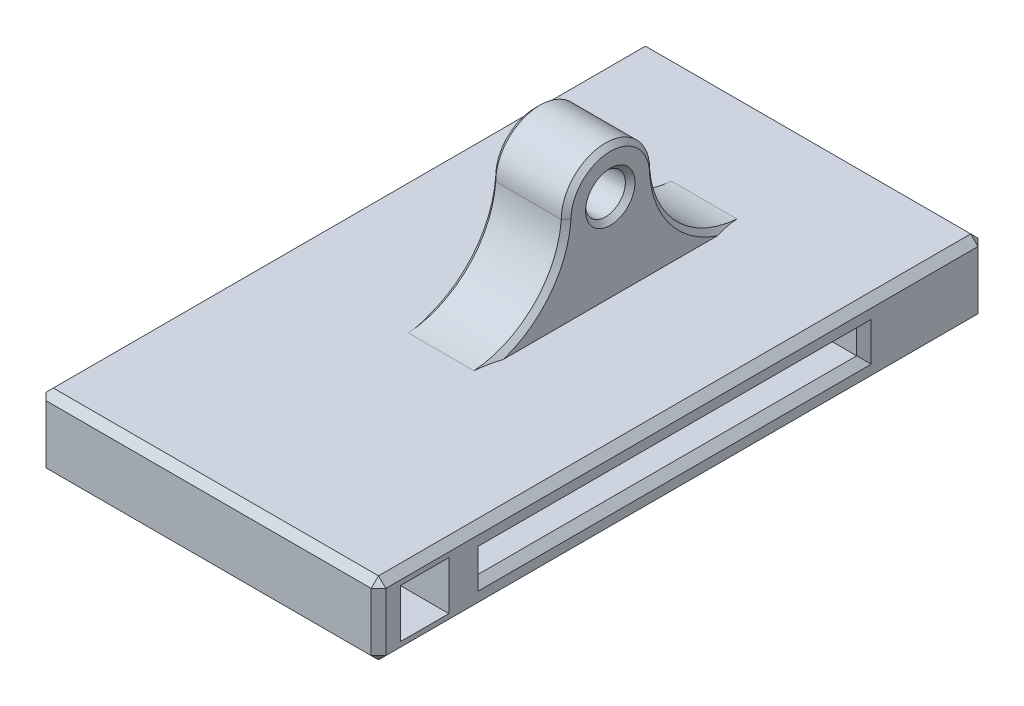
SolidWorks part; units mm, degrees
ref_plane "정면" through (0, 0, 0) normal (0, 0, 1) x (1, 0, 0)
ref_plane "윗면" through (0, 0, 0) normal (0, 1, 0) x (1, 0, 0)
ref_plane "우측면" through (0, 0, 0) normal (1, 0, 0) x (0, 0, -1)
sketch "스케치1" plane through (0, 0, 0) normal (0, 1, 0) x (1, 0, 0)
  line L1 (-35, -30) -> (35, -30)
  line L2 (-35, -30) -> (-35, 30)
  line L3 (-35, 30) -> (35, 30)
  line L4 (35, -30) -> (35, 30)
  line L5 (-35, -30) -> (35, 30) construction
  line L6 (-35, 30) -> (35, -30) construction
  point P0 (0, 0)
  dimension "D1" = 60
  dimension "D2" = 70
extrude "보스-돌출1" add sketch "스케치1" along normal blind 15
sketch "스케치2" plane through (0, 0, 0) normal (1, 0, 0) x (0, 0, -1)
  line L0 (0, 15) -> (0, 33) construction
  line L3 (30, 15) -> (-30, 15)
  circle A0 centre (0, 33) radius 4.1
  circle A1 centre (0, 33) radius 9.1
  arc A2 (9.1, 33) -> (30, 15) centre (28.5463, 34.4457) ccw
  arc A3 (-9.1, 33) -> (-30, 15) centre (-28.5463, 34.4457) cw
  dimension "D1" = 18.2
extrude "보스-돌출3" add sketch "스케치2" along normal mid plane 15.5
sketch "스케치3" plane through (0, 0, 0) normal (1, 0, 0) x (0, 0, -1)
  line L0 (0, 15) -> (0, 0) construction
  line L1 (27.0927, 15) -> (-27.0927, 15) construction
  line L3 (25, 5) -> (-25, 5)
  line L4 (25, 5) -> (25, 10)
  line L5 (25, 10) -> (-25, 10)
  line L6 (-25, 5) -> (-25, 10)
  line L7 (25, 5) -> (-25, 10) construction
  line L8 (25, 10) -> (-25, 5) construction
  point P5 (0, 7.5)
  dimension "D1" = 5
  dimension "D2" = 50
extrude "컷-돌출1" cut sketch "스케치3" against normal through all both and the other way through all
ref_plane "평면1" through (0, 0, 0) normal (0, -1, 0) x (-1, 0, 0)
sketch "스케치5" plane through (0, 0, 0) normal (0, -1, 0) x (-1, 0, 0)
  line L0 (-35, 30) -> (35, 30) construction
  line L1 (-35, 30) -> (35, 30)
  line L2 (-35, 30) -> (-35, 50)
  line L3 (-35, 50) -> (35, 50)
  line L4 (35, 30) -> (35, 50)
  line L5 (-35, -30) -> (35, -30)
  line L6 (-35, -30) -> (-35, -75)
  line L7 (-35, -75) -> (35, -75)
  line L8 (35, -30) -> (35, -75)
  line L9 (35, -30) -> (-35, -30) construction
  dimension "D1" = 20
  dimension "D2" = 45
  dimension "D3" = 70
extrude "보스-돌출4" add sketch "스케치5" against normal up to vertex (15 mm away)
ref_plane "평면9" through (35, 0, 0) normal (1, 0, 0) x (0, 0, -1)
sketch "스케치6" plane through (35, 0, 0) normal (1, 0, 0) x (0, 0, -1)
  line L1 (25, 10) -> (-53.0315, 10)
  line L2 (25, 10) -> (25, 5)
  line L3 (25, 5) -> (-53.0315, 5)
  line L4 (-53.0315, 10) -> (-53.0315, 5)
  point P1 (25, 10)
  point P2 (25, 5)
extrude "컷-돌출2" cut sketch "스케치6" against normal through all both and the other way through all
chamfer "모따기5" distance 1.5 angle 45 19 edges at (35, 7.5, -25) (35, 10, 14.0158) (35, 7.5, 53.0315) (35, 5, 14.0158) (-35, 7.5, -25) (-35, 10, 14.0158) (-35, 7.5, 53.0315) (-35, 5, 14.0158) (35, 7.5, 75) (35, 0, 12.5) (35, 15, 12.5) (35, 7.5, -50) (0, 0, 75) (0, 15, 75) (-35, 0, 12.5) (-35, 15, 12.5) (0, 0, -50) (0, 15, -50) (-35, 7.5, -50)
chamfer "모따기6" distance 1.5 angle 45 1 edges at (-35, 7.5, 75)
chamfer "모따기7" distance 1 angle 45 6 edges at (7.75, 33, -4.1) (7.75, 42.1, 0) (7.75, 20.66, 14.7549) (-7.75, 33, -4.1) (-7.75, 20.66, -14.7549) (-7.75, 42.1, 0)
sketch "스케치7" plane through (35, 0, 0) normal (1, 0, 0) x (0, 0, -1)
  line L1 (-70.5, 12.5) -> (-60.5, 12.5)
  line L2 (-70.5, 12.5) -> (-70.5, 2.5)
  line L3 (-70.5, 2.5) -> (-60.5, 2.5)
  line L4 (-60.5, 12.5) -> (-60.5, 2.5)
  line L5 (-70.5, 12.5) -> (-60.5, 2.5) construction
  line L6 (-70.5, 2.5) -> (-60.5, 12.5) construction
  line L7 (48.5, 13.5) -> (-73.5, 13.5) construction
  line L8 (-73.5, 13.5) -> (-73.5, 1.5) construction
  point P0 (-65.5, 7.5)
  dimension "D1" = 10
  dimension "D2" = 10
  dimension "D3" = 6
  dimension "D4" = 8
extrude "컷-돌출3" cut sketch "스케치7" against normal blind 10 contours L1 L4 L3 L2
